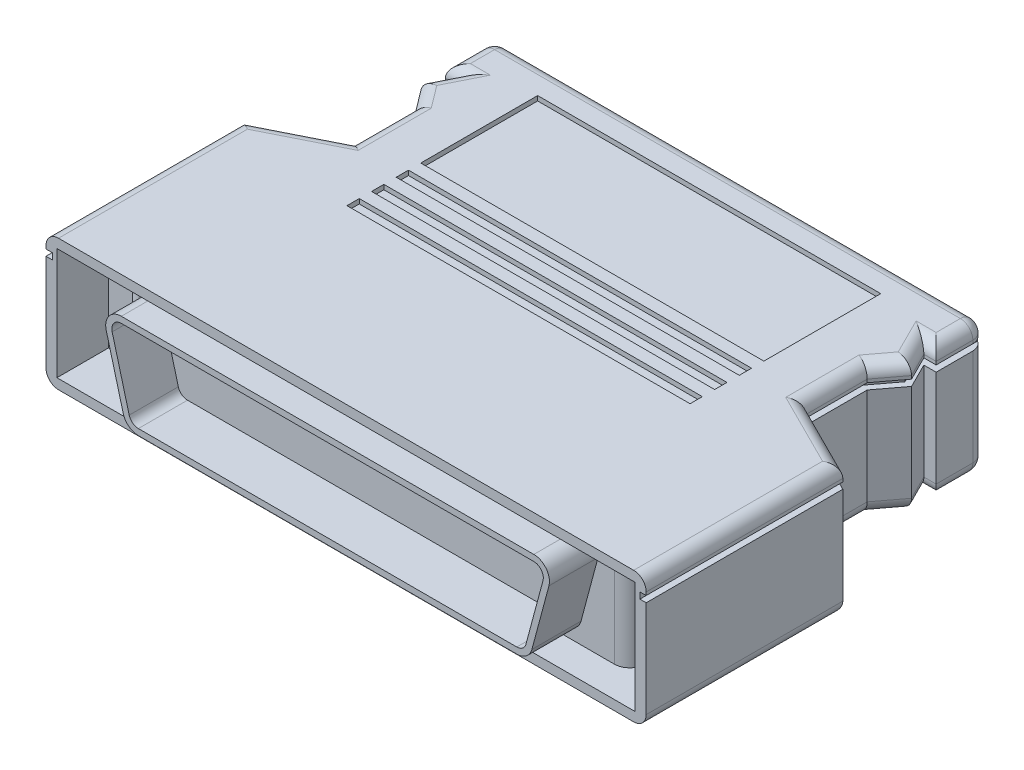
SolidWorks part; units mm, degrees
ref_plane "Front Plane" through (0, 0, 0) normal (0, 0, 1) x (1, 0, 0)
ref_plane "Top Plane" through (0, 0, 0) normal (0, 1, 0) x (1, 0, 0)
ref_plane "Right Plane" through (0, 0, 0) normal (1, 0, 0) x (0, 0, -1)
sketch "Body Outline" plane through (0, 0, 0) normal (0, 1, 0) x (1, 0, 0)
  line L0 (-24.384, 0) -> (24.384, 0)
  line L1 (24.384, 0) -> (24.384, 15.9766)
  line L2 (-19.939, 32.004) -> (19.939, 32.004)
  line L3 (19.939, 28.006) -> (18.9408, 28.006)
  line L4 (24.384, 15.9766) -> (18.3896, 18.9763)
  line L5 (18.3896, 18.9763) -> (18.3896, 23.9547)
  line L6 (19.939, 32.004) -> (19.939, 28.006)
  line L7 (18.3896, 23.9547) -> (19.939, 26.0096)
  line L8 (0, 0) -> (0, 32.004) construction
  line L9 (19.939, 26.0096) -> (18.9408, 28.006)
  line L10 (-19.939, 28.006) -> (-18.9408, 28.006)
  line L11 (-24.384, 0) -> (-24.384, 15.9766)
  line L12 (-24.384, 15.9766) -> (-18.3896, 18.9763)
  line L13 (-18.3896, 18.9763) -> (-18.3896, 23.9547)
  line L14 (-18.3896, 23.9547) -> (-19.939, 26.0096)
  line L15 (-19.939, 26.0096) -> (-18.9408, 28.006)
  line L16 (-19.939, 32.004) -> (-19.939, 28.006)
  point P3 (0, 0)
  point P5 (19.939, 28.006)
  point P8 (0, 32.004)
  point P9 (24.384, 15.9766)
  point P10 (18.3896, 18.9763)
  dimension "D1" = 48.768
  dimension "D2" = 3.998
  dimension "D3" = 39.878
  dimension "D4" = 15.9766
  dimension "D5" = 2.9997
  dimension "D6" = 5.9944
  dimension "D7" = 4.9784
  dimension "D8" = 5.9944
  dimension "D9" = 0.9982
extrude "Connector Body" add sketch "Body Outline" along normal mid plane 10.668
ref_plane "Split Line Plane" through (0, 3.556, 0) normal (0, -1, 0) x (1, 0, 0)
sketch "Split Line Profile" plane through (0, 3.556, 0) normal (0, -1, 0) x (1, 0, 0)
  line L16 (-24.384, 0) -> (-24.384, -15.9766)
  line L17 (24.384, 0) -> (-24.384, 0)
  line L18 (24.384, -15.9766) -> (24.384, 0)
  line L19 (18.3896, -18.9763) -> (24.384, -15.9766)
  line L20 (18.3896, -23.9547) -> (18.3896, -18.9763)
  line L21 (19.939, -26.0096) -> (18.3896, -23.9547)
  line L22 (18.9408, -28.006) -> (19.939, -26.0096)
  line L23 (19.939, -28.006) -> (18.9408, -28.006)
  line L24 (19.939, -32.004) -> (19.939, -28.006)
  line L25 (-19.939, -32.004) -> (19.939, -32.004)
  line L26 (-19.939, -28.006) -> (-19.939, -32.004)
  line L27 (-18.9408, -28.006) -> (-19.939, -28.006)
  line L28 (-19.939, -26.0096) -> (-18.9408, -28.006)
  line L29 (-18.3896, -23.9547) -> (-19.939, -26.0096)
  line L30 (-18.3896, -18.9763) -> (-18.3896, -23.9547)
  line L31 (-24.384, -15.9766) -> (-18.3896, -18.9763)
  line L32 (-24.384, 0) -> (-24.384, -15.9766)
  line L42 (-19.939, -28.006) -> (-19.939, -32.004)
  line L43 (-18.9408, -28.006) -> (-19.939, -28.006)
  line L44 (-19.939, -26.0096) -> (-18.9408, -28.006)
  line L45 (-18.3896, -23.9547) -> (-19.939, -26.0096)
  line L46 (-18.3896, -18.9763) -> (-18.3896, -23.9547)
  line L47 (-24.384, -15.9766) -> (-18.3896, -18.9763)
  dimension "D1" = 0
sketch "Split Line Cut" plane through (0, 0, 0) normal (0, 0, 1) x (1, 0, 0)
  line L0 (-24.384, 3.556) -> (-24.384, 4.064)
  line L1 (-24.384, 5.334) -> (-24.384, -5.334) construction
  line L2 (-24.384, 4.064) -> (-23.876, 4.064)
  line L3 (-23.876, 4.064) -> (-23.876, 3.556)
  line L4 (-23.876, 3.556) -> (-24.384, 3.556)
  dimension "D1" = 0.508
  dimension "D2" = 0.508
sweep "Split Line Left" cut profiles "Split Line Cut" path "Split Line Profile"
mirror "Split Line Right" about plane through (0, 0, 0) normal (1, 0, 0) of "Split Line Left"
sketch "Markings Outline" plane through (0, 5.334, 0) normal (0, 1, 0) x (1, 0, 0)
  line L0 (19.939, 32.004) -> (-19.939, 32.004) construction
  line L1 (-19.939, 32.004) -> (-19.939, 28.006) construction
  line L2 (19.939, 28.006) -> (19.939, 32.004) construction
  line L4 (-13.939, 29.5057) -> (13.939, 29.5057)
  line L5 (-13.939, 29.5057) -> (-13.939, 20.0086)
  line L6 (-13.939, 20.0086) -> (13.939, 20.0086)
  line L7 (13.939, 29.5057) -> (13.939, 20.0086)
  line L8 (-13.939, 19.0089) -> (13.939, 19.0089)
  line L9 (-13.939, 19.0089) -> (-13.939, 18.0096)
  line L10 (-13.939, 18.0096) -> (13.939, 18.0096)
  line L11 (13.939, 19.0089) -> (13.939, 18.0096)
  line L12 (-13.939, 17.0099) -> (13.939, 17.0099)
  line L13 (-13.939, 17.0099) -> (-13.939, 16.0098)
  line L14 (-13.939, 16.0098) -> (13.939, 16.0098)
  line L15 (13.939, 17.0099) -> (13.939, 16.0098)
  line L16 (-13.939, 15.01) -> (13.939, 15.01)
  line L17 (-13.939, 15.01) -> (-13.939, 14.0108)
  line L18 (-13.939, 14.0108) -> (13.939, 14.0108)
  line L19 (13.939, 15.01) -> (13.939, 14.0108)
  point P0 (-13.939, 29.5057)
  point P1 (13.939, 20.0086)
  point P12 (-13.939, 19.0089)
  point P13 (13.939, 18.0096)
  point P18 (-13.939, 17.0099)
  point P19 (13.939, 16.0098)
  point P24 (-13.939, 15.01)
  point P25 (13.939, 14.0108)
  dimension "D1" = 2.4983
  dimension "D2" = 6
  dimension "D3" = 9.4971
  dimension "D4" = 6
  dimension "D5" = 0.9997
  dimension "D6" = 1.999
  dimension "D7" = 0.9997
  dimension "D8" = 1.9999
  dimension "D9" = 1.999
  dimension "D10" = 0.9997
extrude "Markings" cut sketch "Markings Outline" against normal blind 0.381
mirror "Mirror Markings" about plane through (0, 0, 0) normal (0, 1, 0) of "Markings"
sketch "Plug Countersink Outline" plane through (0, 0, 0) normal (0, 0, 1) x (1, 0, 0)
  line L0 (-24.384, 3.556) -> (-24.384, -5.334) construction
  line L1 (-24.384, -5.334) -> (24.384, -5.334) construction
  line L2 (-24.384, 5.334) -> (24.384, 5.334) construction
  line L3 (24.384, 3.556) -> (24.384, -5.334) construction
  line L5 (-23.495, -4.5466) -> (23.495, -4.5466)
  line L6 (-23.495, -4.5466) -> (-23.495, 4.5466)
  line L7 (-23.495, 4.5466) -> (23.495, 4.5466)
  line L8 (23.495, -4.5466) -> (23.495, 4.5466)
  point P0 (-23.495, -4.5466)
  point P5 (23.495, 4.5466)
  dimension "D1" = 0.889
  dimension "D2" = 0.7874
  dimension "D3" = 0.7874
  dimension "D4" = 0.889
extrude "Plug Countersink" cut sketch "Plug Countersink Outline" against normal blind 4.191
sketch "Plug Base Outline" plane through (0, 0, -4.191) normal (0, 0, 1) x (1, 0, 0)
  line L1 (-23.495, -4.5466) -> (23.495, -4.5466) construction
  line L2 (-23.495, 4.5466) -> (-23.495, -4.5466) construction
  line L3 (23.495, 4.5466) -> (-23.495, 4.5466) construction
  line L4 (23.495, -4.5466) -> (23.495, 4.5466) construction
  line L6 (-20.574, -4.5466) -> (20.574, -4.5466)
  line L7 (-20.574, -4.5466) -> (-20.574, 4.5466)
  line L8 (-20.574, 4.5466) -> (20.574, 4.5466)
  line L9 (20.574, -4.5466) -> (20.574, 4.5466)
  point P0 (-20.574, -4.5466)
  point P5 (20.574, 4.5466)
  dimension "D1" = 2.921
  dimension "D2" = 2.921
extrude "Plug Base" add sketch "Plug Base Outline" along normal blind 1.7018
fillet "Fillet1" radius 1.27 2 edges at (-20.574, 0, -2.4892) (20.574, 0, -2.4892)
sketch "Plug Outline" plane through (0, 0, -2.4892) normal (0, 0, 1) x (1, 0, 0)
  line L0 (19.304, 4.5466) -> (-19.304, 4.5466) construction
  line L1 (-19.304, 4.5466) -> (-19.304, -4.5466) construction
  line L2 (19.304, -4.5466) -> (19.304, 4.5466) construction
  line L4 (-16.76, 3.8967) -> (16.7598, 3.8988)
  line L5 (17.9866, 2.3001) -> (16.6019, -2.8677)
  line L6 (15.3752, -3.809) -> (-15.3752, -3.811)
  line L7 (-16.602, -2.8697) -> (-17.9867, 2.298)
  line L8 (-18.415, 3.8966) -> (-18.415, -3.9116) construction
  line L9 (18.415, 3.8989) -> (18.415, -3.8989) construction
  arc A0 (-17.9867, 2.298) -> (-16.76, 3.8967) centre (-16.7599, 2.6267) cw
  arc A1 (-16.602, -2.8697) -> (-15.3752, -3.811) centre (-15.3753, -2.541) ccw
  arc A2 (16.6019, -2.8677) -> (15.3752, -3.809) centre (15.3752, -2.539) cw
  arc A3 (16.7598, 3.8988) -> (17.9866, 2.3001) centre (16.7599, 2.6288) cw
  point P0 (-18.415, 3.8966)
  point P1 (-16.3497, -3.811)
  point P2 (16.3497, -3.809)
  point P3 (18.415, 3.8989)
  point P10 (0, 0)
  point P18 (-18.415, 3.8966)
  point P21 (-16.3497, -3.811)
  point P24 (16.3497, -3.809)
  point P27 (18.415, 3.8989)
  dimension "D9" = 1.27
  dimension "D1" = 0.65
  dimension "D2" = 0.889
  dimension "D3" = 0.889
  dimension "D4" = 0.6477
  dimension "D5" = 15
  dimension "D6" = 3.81
  dimension "D10" = 15
extrude "Plug - Thin Feature" add sketch "Plug Outline" along normal blind 3.9929 thin thin type one direction reverse wall 0.4991
fillet "Fillet2" radius 1.016 34 edges at (24.384, -5.334, -7.9883) (21.3868, -5.334, -17.4765) (18.3896, -5.334, -21.4655) (19.1643, -5.334, -24.9822) (19.4399, -5.334, -27.0078) (19.4399, -5.334, -28.006) (19.939, -5.334, -30.005) (0, -5.334, -32.004) (19.939, 4.699, -32.004) (19.939, -0.889, -32.004) (-19.939, 4.699, -32.004) (-19.939, -0.889, -32.004) (-19.939, -5.334, -30.005) (-19.4399, -5.334, -28.006) (-19.4399, -5.334, -27.0078) (-19.1643, -5.334, -24.9822) (-18.3896, -5.334, -21.4655) (-21.3868, -5.334, -17.4765) (-24.384, -5.334, -7.9883) (24.384, 5.334, -7.9883) (21.3868, 5.334, -17.4765) (18.3896, 5.334, -21.4655) (19.1643, 5.334, -24.9822) (19.4399, 5.334, -27.0078) (19.4399, 5.334, -28.006) (19.939, 5.334, -30.005) (0, 5.334, -32.004) (-19.939, 5.334, -30.005) (-19.4399, 5.334, -28.006) (-19.4399, 5.334, -27.0078) (-19.1643, 5.334, -24.9822) (-18.3896, 5.334, -21.4655) (-21.3868, 5.334, -17.4765) (-24.384, 5.334, -7.9883)
sketch "Cable Slot Outline" plane through (0, 0, -32.004) normal (0, 0, -1) x (-1, 0, 0)
  line L0 (-19.939, 3.556) -> (-19.939, -5.334) construction
  line L1 (19.939, 3.556) -> (19.939, -5.334) construction
  line L2 (-19.939, 5.334) -> (19.939, 5.334) construction
  line L3 (-19.939, -5.334) -> (19.939, -5.334) construction
  line L5 (-17.8392, 2.032) -> (17.8384, 2.032)
  line L6 (-17.8392, 2.032) -> (-17.8392, -1.016)
  line L7 (-17.8392, -1.016) -> (17.8384, -1.016)
  line L8 (17.8384, 2.032) -> (17.8384, -1.016)
  point P0 (-17.8392, 2.032)
  point P1 (17.8384, -1.016)
  dimension "D1" = 2.0998
  dimension "D2" = 2.1006
  dimension "D3" = 3.302
  dimension "D4" = 4.318
extrude "Ribbon Cable Slot" cut sketch "Cable Slot Outline" against normal blind 13.0277
sketch "Mark Point For CPoint" plane through (0, 0, -18.9763) normal (0, 0, -1) x (-1, 0, 0)
  point P0 (0, 0.508)
other "CPoint1" parameters "Diameter"=25.4, "StubLength"=0
ref_axis "Axis1" through (0, 0.508, -28.9763) along (0, 0, 1)
